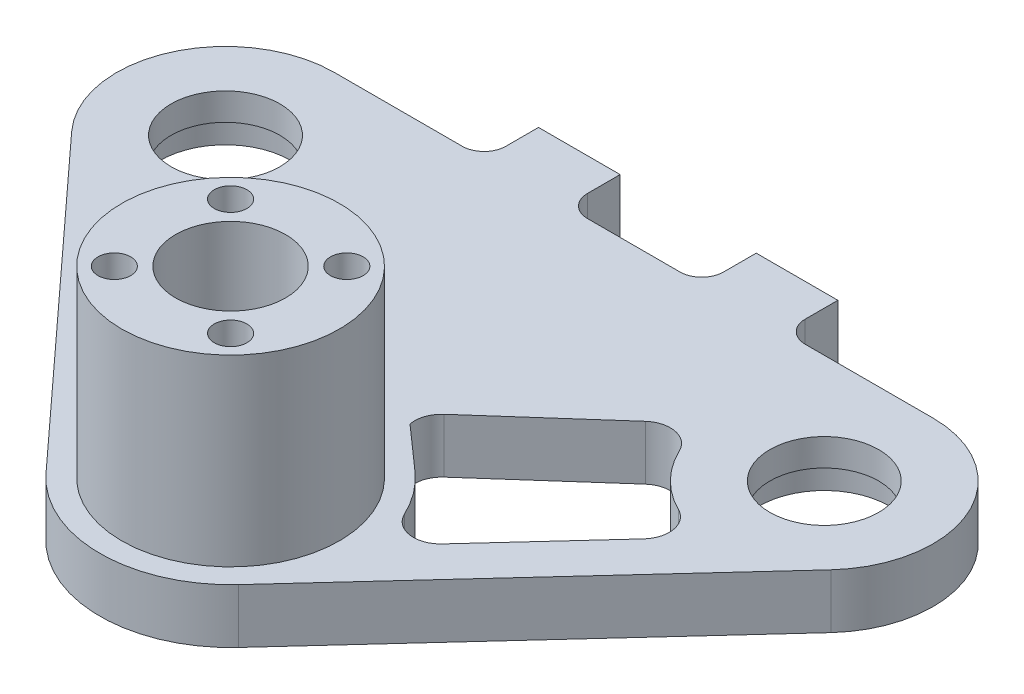
SolidWorks part; units mm, degrees
material "PLA Infill"
ref_plane "Front Plane" through (0, 0, 0) normal (0, 0, 1) x (1, 0, 0)
ref_plane "Top Plane" through (0, 0, 0) normal (0, 1, 0) x (1, 0, 0)
ref_plane "Right Plane" through (0, 0, 0) normal (1, 0, 0) x (0, 0, -1)
sketch "Sketch1" plane through (0, 0, 0) normal (0, 1, 0) x (1, 0, 0)
  line L0 (0, 0) -> (55, 54.0672) construction
  line L1 (55, 54.0672) -> (-55, 54.0672) construction
  line L2 (-55, 54.0672) -> (0, 0) construction
  line L3 (-69.7415, 40.551) -> (-17.6898, -16.2194)
  line L4 (-41.7379, 69.0378) -> (15.9145, 17.9646)
  line L5 (-47.6255, 28.2677) -> (-29.9271, 8.9649)
  line L6 (-29.0781, 47.135) -> (-9.4754, 29.7694)
  circle A0 centre (0, 0) radius 10.1
  circle A1 centre (-55, 54.0672) radius 10
  circle A2 centre (0, 0) radius 24 construction
  circle A3 centre (-55, 54.0672) radius 20 construction
  arc A4 (-69.7415, 40.551) -> (-41.7379, 69.0378) centre (-55, 54.0672) cw
  arc A5 (-17.6898, -16.2194) -> (15.9145, 17.9646) centre (0, 0) ccw
  arc A6 (-46.1521, 36.1308) -> (-36.9149, 45.5274) centre (-55, 54.0672) ccw
  arc A7 (-21.7173, 10.2157) -> (-10.5856, 21.5394) centre (0, 0) cw
  arc A8 (-29.9271, 8.9649) -> (-21.7173, 10.2157) centre (-26.2417, 12.3439) ccw
  arc A9 (-9.4754, 29.7694) -> (-10.5856, 21.5394) centre (-12.7909, 26.0268) cw
  arc A10 (-29.0781, 47.135) -> (-36.9149, 45.5274) centre (-32.3936, 43.3924) ccw
  arc A11 (-47.6255, 28.2677) -> (-46.1521, 36.1308) centre (-43.9401, 31.6467) cw
  point P22 (-23.8825, 2.3723)
  point P25 (-2.7804, 23.8384)
  point P28 (-35.0663, 52.4399)
  point P31 (-53.032, 34.1643)
  dimension "D3" = 20.2
  dimension "D4" = 20
  dimension "D5" = 48
  dimension "D6" = 40
  dimension "D9" = 5
  dimension "D1" = 77.125
  dimension "D2" = 110
  dimension "D7" = 8
  dimension "D8" = 8
extrude "Main Body" add sketch "Sketch1" along normal blind 10
sketch "Sketch2" plane through (0, 0, 0) normal (0, -1, 0) x (1, 0, 0)
  circle A0 centre (-55, -54.0672) radius 10 construction
  circle A1 centre (-55, -54.0672) radius 10 construction
  circle A2 centre (-55, -54.0672) radius 12
  dimension "D1" = 24
extrude "Bearing Recess" cut sketch "Sketch2" against normal blind 5
sketch "Sketch3" plane through (0, 0, 0) normal (0, -1, 0) x (1, 0, 0)
  circle A0 centre (0, 0) radius 21.5
  circle A1 centre (0, 0) radius 10.1
  circle A2 centre (0, 0) radius 10.1 construction
  dimension "D1" = 43
extrude "Standoff Section" add sketch "Sketch3" along normal blind 1.5
sketch "Sketch9" plane through (0, 10, 0) normal (0, 1, 0) x (1, 0, 0)
  circle A0 centre (0, 0) radius 20
  circle A1 centre (0, 0) radius 10.1
  dimension "D1" = 40
  dimension "D2" = 20.2
extrude "Boss-Extrude1" add sketch "Sketch9" along normal blind 33.7
ref_plane "Mirror Plane" through (0, 0, 0) normal (1, 0, 0) x (0, 0, -1)
sketch "Sketch6" plane through (0, 0, 0) normal (0, 1, 0) x (1, 0, 0)
  line L0 (-55, 74.0672) -> (0, 74.0672) construction
  line L1 (0, -30.36) -> (0, 30.36) construction
  line L2 (0, 74.0672) -> (0, 32.063)
  line L3 (-41.7379, 69.0378) -> (15.9145, 17.9646) construction
  line L4 (0, 32.063) -> (-41.7379, 69.0378)
  line L5 (-20, 84.0672) -> (-20, 74.0672) construction
  line L6 (-27.5, 74.0672) -> (-12.5, 74.0672) construction
  line L7 (-27.5, 78.0672) -> (-27.5, 84.0672)
  line L8 (-27.5, 84.0672) -> (-12.5, 84.0672)
  line L9 (-12.5, 78.0672) -> (-12.5, 84.0672)
  line L10 (-55, 74.0672) -> (-31.5, 74.0672)
  line L11 (-8.5, 74.0672) -> (0, 74.0672)
  arc A0 (-41.7379, 69.0378) -> (-69.7415, 40.551) centre (-55, 54.0672) ccw construction
  arc A1 (-41.7379, 69.0378) -> (-69.7415, 40.551) centre (-55, 54.0672) ccw construction
  arc A2 (-55, 74.0672) -> (-41.7379, 69.0378) centre (-55, 54.0672) cw
  arc A3 (-8.5, 74.0672) -> (-12.5, 78.0672) centre (-8.5, 78.0672) cw
  arc A4 (-31.5, 74.0672) -> (-27.5, 78.0672) centre (-31.5, 78.0672) ccw
  dimension "D4" = 4
  dimension "D1" = 10
  dimension "D2" = 20
  dimension "D3" = 15
extrude "Extra Geometry" add sketch "Sketch6" along normal blind 10
sketch "Sketch8" plane through (0, 0, -84.0672) normal (0, 0, -1) x (-1, 0, 0)
  line L0 (20, 10) -> (20, 0) construction
  line L1 (12.5, 10) -> (27.5, 10) construction
  line L2 (12.5, 0) -> (27.5, 0) construction
  circle A0 centre (20, 5) radius 2
  point P9 (20, 5)
  dimension "D1" = 4
extrude "Cut-Extrude1" cut sketch "Sketch8" against normal blind 6
mirror "Mirror2" about plane through (0, 0, 0) normal (1, 0, 0) of bodies 109 107
sketch "Sketch4" plane through (0, -1.5, 0) normal (0, -1, 0) x (1, 0, 0)
  line L0 (0, 0) -> (50000, 0) construction
  line L1 (55, -54.0672) -> (-55, -54.0672) construction
  line L2 (-10.6773, 10.6773) -> (0, 0) construction
  circle A0 centre (-10.6773, 10.6773) radius 3
  circle A2 centre (10.6773, 10.6773) radius 3
  circle A3 centre (10.6773, -10.6773) radius 3
  circle A4 centre (-10.6773, -10.6773) radius 3
  dimension "D1" = 6
  dimension "D2" = 15.1
  dimension "D3" = 45
  dimension "D4" = 4
extrude "M6 Bolt holes" cut sketch "Sketch4" against normal through all
